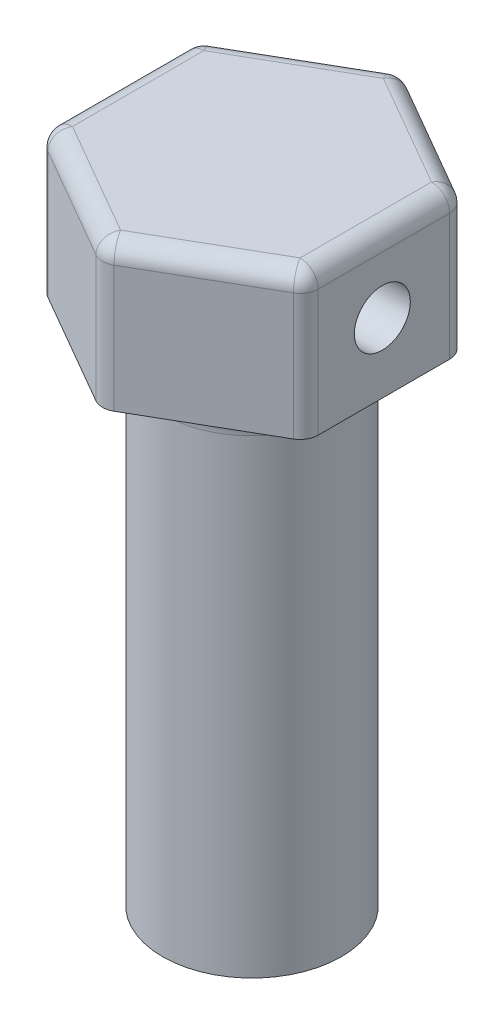
SolidWorks part; units mm, degrees
ref_plane "Front Plane" through (0, 0, 0) normal (0, 0, 1) x (1, 0, 0)
ref_plane "Top Plane" through (0, 0, 0) normal (0, 1, 0) x (1, 0, 0)
ref_plane "Right Plane" through (0, 0, 0) normal (1, 0, 0) x (0, 0, -1)
sketch "Sketch1" plane through (0, 0, 0) normal (0, 1, 0) x (1, 0, 0)
  line L1 (7.3, -4.2147) -> (7.3, 4.2147)
  line L2 (7.3, 4.2147) -> (0, 8.4293)
  line L3 (0, 8.4293) -> (-7.3, 4.2147)
  line L4 (-7.3, 4.2147) -> (-7.3, -4.2147)
  line L5 (-7.3, -4.2147) -> (0, -8.4293)
  line L6 (0, -8.4293) -> (7.3, -4.2147)
  circle A0 centre (0, 0) radius 7.3 construction
  dimension "D1" = 14.6
extrude "Boss-Extrude1" add sketch "Sketch1" along normal blind 8
sketch "Sketch2" plane through (0, 0, 0) normal (0, -1, 0) x (1, 0, 0)
  line L0 (-1.15, 1.0392) -> (-1.15, -1.0392)
  line L1 (-7.3, -4.2147) -> (-7.3, 4.2147) construction
  arc A0 (-1.15, -1.0392) -> (-1.15, 1.0392) centre (0, 0) ccw
  circle A1 centre (0, 0) radius 4.95
  dimension "D1" = 3.1
  dimension "D2" = 9.9
  dimension "D3" = 1.15
extrude "Boss-Extrude2" add sketch "Sketch2" along normal blind 28 contours A1 | A0 L0
fillet "Fillet1" radius 2 1 edges at (0, 0, 4.95)
sketch "Sketch3" plane through (7.3, 0, 0) normal (1, 0, 0) x (0, 0, -1)
  line L0 (-6.95, 0) -> (6.95, 0) construction
  line L1 (4.2147, 8) -> (4.2147, 0) construction
  circle A0 centre (-0.0853, 3.85) radius 1.55
  dimension "D1" = 3.1
  dimension "D2" = 3.85
  dimension "D3" = 4.3
extrude "Cut-Extrude1" cut sketch "Sketch3" against normal through all
fillet "Fillet2" radius 1 12 edges at (-3.65, 8, 6.322) (-7.3, 8, 0) (-3.65, 8, -6.322) (3.65, 8, -6.322) (7.3, 8, 0) (3.65, 8, 6.322) (-7.3, 4, -4.2147) (0, 4, -8.4293) (7.3, 4, -4.2147) (7.3, 4, 4.2147) (0, 4, 8.4293) (-7.3, 4, 4.2147)
sketch "Sketch4" plane through (0, 0, 0) normal (1, 0, 0) x (0, 0, -1)
  line L1 (-16.1086, 1.5942) -> (18.1695, 1.5942)
  line L2 (-16.1086, 1.5942) -> (-16.1086, -34.824)
  line L3 (-16.1086, -34.824) -> (18.1695, -34.824)
  line L4 (18.1695, 1.5942) -> (18.1695, -34.824)
extrude "Cut-Extrude2" [suppressed] cut sketch "Sketch4" against normal through all both and the other way through all
sketch "Sketch5" plane through (0, -28, 0) normal (0, -1, 0) x (1, 0, 0)
  circle A0 centre (0, 0) radius 1.55
  dimension "D1" = 3.1
extrude "Cut-Extrude3" cut sketch "Sketch5" against normal blind 4
equation "\"1.ø15\"=1.5"
